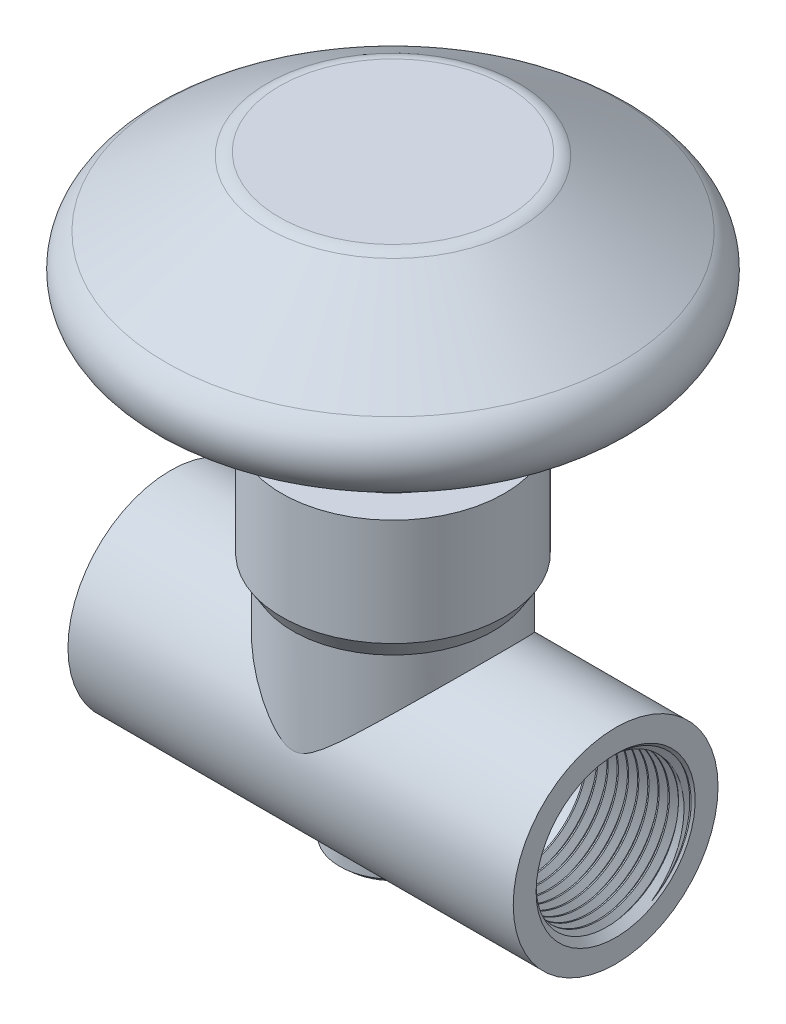
SolidWorks part; units mm, degrees
note: The reader was unsure of these and kept them because the rebuilt part matched: shared geometry of "Sketch9<2>".
ref_plane "Front" through (0, 0, 0) normal (0, 0, 1) x (1, 0, 0)
ref_plane "Top" through (0, 0, 0) normal (0, 1, 0) x (1, 0, 0)
ref_plane "Right" through (0, 0, 0) normal (1, 0, 0) x (0, 0, -1)
sketch "Sketch1" plane through (0, 0, 0) normal (0, 0, 1) x (1, 0, 0)
  line L0 (-31.75, 0) -> (31.75, 0) construction
  line L1 (-31.75, -11.0901) -> (-31.75, 11.0901) construction
  line L2 (31.75, -11.0901) -> (31.75, 11.0901) construction
  line L3 (-31.75, 11.0901) -> (-31.75, 14.605)
  line L6 (-31.75, 14.605) -> (31.75, 14.605)
  line L9 (31.75, 14.605) -> (31.75, 11.0901)
  line L10 (0, 0) -> (0, 14.605) construction
  line L11 (-31.75, 11.0901) -> (-18.194, 10.668)
  line L12 (-18.194, 10.668) -> (18.194, 10.668)
  line L13 (18.194, 10.668) -> (31.75, 11.0901)
  line L14 (-18.194, 10.668) -> (-31.75, 10.668) construction
  dimension "D2" = 63.5
  dimension "D4" = 29.21
  dimension "D6" = 1.783
  dimension "D7" = 13.556
  dimension "D8" = 21.336
revolve "Revolve1" add sketch "Sketch1" angle 360 about L0
sketch "Sketch2" plane through (0, 0, 0) normal (0, 0, 1) x (1, 0, 0)
  line L0 (0, -17.78) -> (0, 14.605)
  line L1 (31.75, 14.605) -> (-31.75, 14.605) construction
  line L2 (0, 14.605) -> (-9.525, 14.605)
  line L3 (-9.525, 14.605) -> (-9.525, 35.56)
  line L4 (-9.525, 35.56) -> (-15.875, 35.56)
  line L5 (-15.875, 35.56) -> (-15.875, 20.32)
  line L6 (-15.875, 20.32) -> (-14.2875, 17.78)
  line L7 (-14.2875, 17.78) -> (-14.2875, 0)
  line L8 (-31.75, -14.605) -> (31.75, -14.605) construction
  line L10 (-9.525, 35.56) -> (9.525, 35.56) construction
  line L11 (0, 35.56) -> (0, 14.605) construction
  line L12 (-7.62, -14.605) -> (-7.62, 0)
  line L13 (-7.62, 0) -> (-14.2875, 0)
  arc A0 (-7.62, -14.605) -> (0, -17.78) centre (0, -7.0485) ccw
  dimension "D1" = 3.175
  dimension "D2" = 31.75
  dimension "D3" = 28.575
  dimension "D4" = 15.24
  dimension "D5" = 17.78
  dimension "D6" = 19.05
  dimension "D7" = 50.165
  dimension "D8" = 15.24
revolve "Revolve2" add sketch "Sketch2" angle 360 about L11
sketch "Sketch3" plane through (0, 0, 0) normal (1, 0, 0) x (0, 0, -1)
  circle A0 centre (0, 0) radius 10.668 construction
  circle A1 centre (0, 0) radius 10.668
extrude "Cut-Extrude1" cut sketch "Sketch3" against normal through all and the other way through all
sketch "Sketch4" plane through (0, 0, 0) normal (0, 0, 1) x (1, 0, 0)
  line L0 (0, 14.605) -> (0, 47.9425)
  line L1 (9.525, 14.605) -> (-9.525, 14.605) construction
  line L2 (0, 14.605) -> (-9.525, 14.605)
  line L3 (-9.525, 14.605) -> (-9.525, 36.6713)
  line L4 (-9.525, 36.6713) -> (-12.7, 36.6713)
  line L5 (-9.525, 35.56) -> (-15.875, 35.56) construction
  line L6 (0, 14.605) -> (0, 0) construction
  line L7 (-12.7, 36.6713) -> (-12.7, 46.8313)
  line L8 (-12.7, 46.8313) -> (-9.525, 46.8313)
  line L9 (-9.525, 46.8313) -> (-8.4138, 47.9425)
  line L10 (-8.4138, 47.9425) -> (0, 47.9425)
  dimension "D1" = 1.1112
  dimension "D2" = 25.4
  dimension "D3" = 10.16
  dimension "D4" = 1.1112
  dimension "D5" = 45
revolve "Revolve3" add sketch "Sketch4" angle 360 about L6
sketch "Sketch5" plane through (0, 46.8313, 0) normal (0, 1, 0) x (1, 0, 0)
  line L0 (-10.2235, 7.5346) -> (-10.2235, -7.5346)
  line L1 (10.2235, 7.5346) -> (10.2235, -7.5346)
  line L2 (-10.2235, 0) -> (10.2235, 0) construction
  circle A0 centre (0, 0) radius 12.7 construction
  arc A1 (-10.2235, 7.5346) -> (-10.2235, -7.5346) centre (0, 0) ccw
  arc A2 (10.2235, -7.5346) -> (10.2235, 7.5346) centre (0, 0) ccw
  dimension "D1" = 20.447
extrude "Cut-Extrude2" cut sketch "Sketch5" against normal up to surface (10.16 mm away) up to face at (-9.525, 36.6713, 0)
sketch "Sketch6" plane through (0, 0, 0) normal (0, 0, 1) x (1, 0, 0)
  line L0 (0, 47.9425) -> (0, 69.85)
  line L1 (8.4138, 47.9425) -> (-8.4138, 47.9425) construction
  line L2 (0, 69.85) -> (-16.2088, 69.85)
  line L3 (-17.9314, 69.342) -> (-32.3834, 60.0076)
  line L4 (0, 47.9425) -> (0, 35.56) construction
  line L5 (15.875, 35.56) -> (-15.875, 35.56) construction
  line L6 (0, 47.9425) -> (-6.35, 47.9425)
  line L7 (-6.35, 47.9425) -> (-6.35, 49.784)
  line L8 (-6.35, 49.784) -> (-29.3687, 49.784)
  line L9 (-34.925, 55.3403) -> (-34.925, 49.784) construction
  line L10 (-34.925, 49.784) -> (-29.3687, 49.784) construction
  line L11 (-34.925, 55.3403) -> (34.925, 55.3403) construction
  arc A0 (-32.3834, 60.0076) -> (-29.3687, 49.784) centre (-29.3687, 55.3403) ccw
  arc A1 (-16.2088, 69.85) -> (-17.9314, 69.342) centre (-16.2088, 66.675) ccw
  point P18 (-17.145, 69.85)
  dimension "D3" = 11.1125
  dimension "D7" = 3.175
  dimension "D1" = 34.29
  dimension "D2" = 20.066
  dimension "D4" = 69.85
  dimension "D5" = 87.63
  dimension "D6" = 12.7
revolve "Revolve4" add sketch "Sketch6" angle 360 about L0
ref_plane "Plane1" through (-18.194, 0, 0) normal (1, 0, 0) x (0, 0, -1)
sketch "Sketch7" plane through (-18.194, 0, 0) normal (1, 0, 0) x (0, 0, -1)
  circle A0 centre (0, 0) radius 10.668 construction
  circle A1 centre (0, 0) radius 10.668
curve "Helix/Spiral1"
sketch "Sketch8" plane through (0, 0, 0) normal (0, 0, 1) x (1, 0, 0)
  line L0 (-18.194, 10.668) -> (-17.6649, 9.7515)
  line L1 (-18.194, 10.668) -> (-18.194, -10.668) construction
  line L2 (-17.6649, 9.7515) -> (-17.4885, 9.7515)
  line L3 (-17.4885, 9.7515) -> (-16.9593, 10.668)
  line L4 (-16.9593, 10.668) -> (-18.194, 10.668)
  line L5 (-17.9294, 10.2097) -> (-17.2239, 10.2097) construction
  line L6 (-17.5767, 10.2097) -> (-17.5767, 9.7515) construction
  dimension "D1" = 60
  dimension "D2" = 0.1764
  dimension "D3" = 0.7056
sketch "Sketch9" plane through (-31.75, 0, 0) normal (-1, 0, 0) x (0, 0, 1)
  line L0 (34.925, 55.3403) -> (-34.925, 55.3402) construction
  line L1 (29.3687, 55.3403) -> (29.3687, 49.784) construction
  line L2 (32.3834, 60.0076) -> (29.3687, 55.3403) construction
  circle A0 centre (0, 0) radius 11.3441
  circle A1 centre (0, 0) radius 11.0901 construction
  arc A2 (29.3687, 49.784) -> (32.3834, 60.0076) centre (29.3687, 55.3403) ccw construction
  arc A3 (-32.3834, 60.0076) -> (-29.3687, 49.784) centre (-29.3687, 55.3403) ccw construction
  arc A4 (29.3687, 49.784) -> (32.3834, 60.0076) centre (29.3687, 55.3403) ccw construction
  dimension "D1" = 0.254
sweep "Sweep1" add profiles "Sketch8" path "Helix/Spiral1"
extrude "Cut-Extrude3" cut sketch "Sketch9" along normal through all
extrude "Cut-Extrude4" cut sketch "Sketch9<2>" against normal through all draft 45
sketch "Sketch9<2>" plane through (-31.75, 0, 0) normal (-1, 0, 0) x (0, 0, 1) same geometry as "Sketch9"
mirror "Mirror1" about plane through (0, 0, 0) normal (1, 0, 0) of "Cut-Extrude4", "Cut-Extrude3", "Sweep1"
